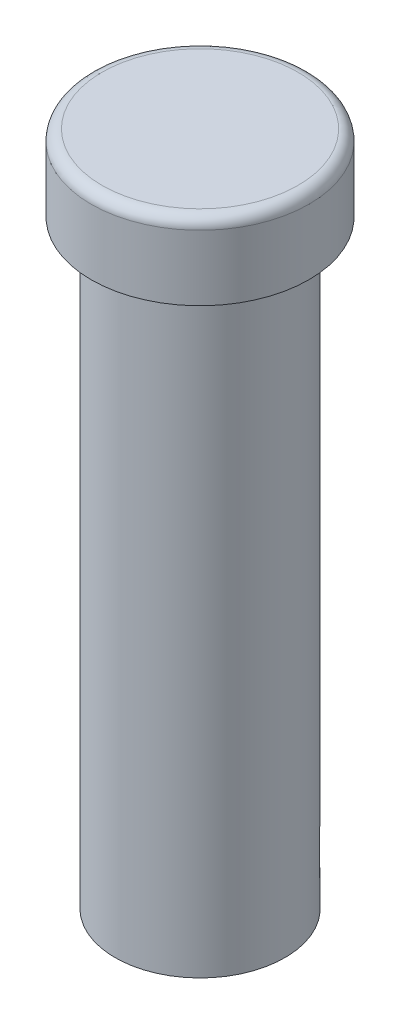
SolidWorks part; units mm, degrees
ref_plane "Front Plane" through (0, 0, 0) normal (0, 0, 1) x (1, 0, 0)
ref_plane "Top Plane" through (0, 0, 0) normal (0, 1, 0) x (1, 0, 0)
ref_plane "Right Plane" through (0, 0, 0) normal (1, 0, 0) x (0, 0, -1)
sketch "Sketch1" plane through (0, 0, 0) normal (0, 1, 0) x (1, 0, 0)
  circle A0 centre (0, 0) radius 12.7
  dimension "D1" = 25.4
extrude "Boss-Extrude1" add sketch "Sketch1" along normal blind 8.89
sketch "Sketch2" plane through (0, 0, 0) normal (0, -1, 0) x (1, 0, 0)
  circle A0 centre (0, 0) radius 9.906
  dimension "D1" = 19.812
extrude "Boss-Extrude2" add sketch "Sketch2" along normal blind 69.85
fillet "Fillet2" radius 1.27 1 edges at (0, 8.89, 12.7)
ref_plane "Plane1" through (0, 0, 2.54) normal (0, 0, 1) x (1, 0, 0)
ref_axis "Axis3" through (0, -69.85, 0) along (0, 1, 0)
sketch "Sketch5" plane through (0, 0, 2.54) normal (0, 0, 1) x (1, 0, 0)
  line L1 (-12.6593, -66.1694) -> (15.7092, -66.1694)
  line L2 (-12.6593, -66.1694) -> (-12.6593, -60.9777)
  line L3 (-12.6593, -60.9777) -> (15.7092, -60.9777)
  line L4 (15.7092, -66.1694) -> (15.7092, -60.9777)
extrude "Cut-Extrude1" cut sketch "Sketch5" against normal blind 69.85 from offset 8.89 offset against normal yes
